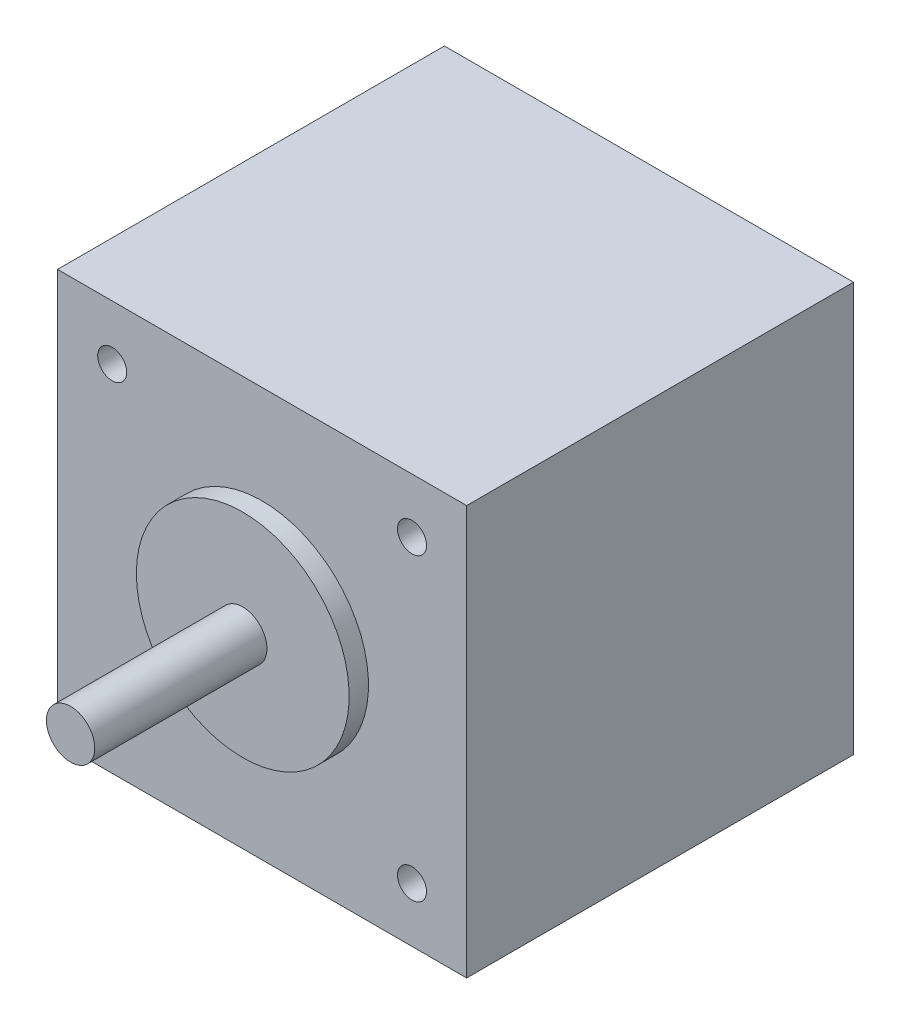
SolidWorks part; units mm, degrees
ref_plane "Спереди" through (0, 0, 0) normal (0, 0, 1) x (1, 0, 0)
ref_plane "Сверху" through (0, 0, 0) normal (0, 1, 0) x (1, 0, 0)
ref_plane "Справа" through (0, 0, 0) normal (1, 0, 0) x (0, 0, -1)
other "Configuration Table"
sketch "Эскиз1" plane through (0, 0, 0) normal (0, 0, 1) x (1, 0, 0)
  line L1 (-21.15, -21.15) -> (21.15, -21.15)
  line L2 (-21.15, -21.15) -> (-21.15, 21.15)
  line L3 (-21.15, 21.15) -> (21.15, 21.15)
  line L4 (21.15, -21.15) -> (21.15, 21.15)
  line L5 (-21.15, -21.15) -> (21.15, 21.15) construction
  line L6 (-21.15, 21.15) -> (21.15, -21.15) construction
  point P0 (0, 0)
  dimension "D1" = 42.3
  dimension "D2" = 42.3
extrude "Корпус" add sketch "Эскиз1" along normal blind 40
sketch "Эскиз2" plane through (0, 0, 0) normal (0, 0, 1) x (1, 0, 0)
  circle A0 centre (0, 0) radius 2.5
extrude "Вал_ПРЕДВ" add sketch "Эскиз2" along normal blind 59.8
sketch "Эскиз3" plane through (0, 0, 0) normal (0, 0, 1) x (1, 0, 0)
  circle A0 centre (0, 0) radius 11
  dimension "D1" = 22
extrude "Буртик_ПРЕДВ" add sketch "Эскиз3" along normal blind 42
sketch "Эскиз4" plane through (0, 0, 0) normal (0, 0, 1) x (1, 0, 0)
  circle A0 centre (0, 0) radius 8
  dimension "D1" = 16
sketch "Эскиз5" plane through (0, 0, 0) normal (0, 0, 1) x (1, 0, 0)
  circle A0 centre (-15.5, -15.5) radius 1.5
  circle A1 centre (-15.5, 15.5) radius 1.5
  circle A2 centre (15.5, -15.5) radius 1.5
  circle A3 centre (15.5, 15.5) radius 1.5
  dimension "D1" = 3
  dimension "D2" = 3
  dimension "D3" = 3
  dimension "D4" = 3
extrude "Крепеж_М3_ПРЕДВ" cut sketch "Эскиз5" against normal blind 4.5 from offset 40
equation "\"Мотор X ширина корпуса\"= 42.3"
equation "\"Мотор X высота корпуса\"= 42.3"
equation "\"Мотор X длина корпуса\"= 40"
equation "\"Мотор X вылет вала\"= 19.8"
equation "\"Мотор Y ширина корпуса\"= 42.3"
equation "\"Мотор Y высота корпуса\"= 42.3"
equation "\"Мотор Y длина корпуса\"= 48"
equation "\"Мотор Y вылет вала\"= 30"
equation "\"Мотор Z ширина корпуса\"= 42"
equation "\"Мотор Z высота корпуса\"= 42"
equation "\"Мотор Z длина корпуса\"= 40"
equation "\"Мотор Z вылет вала\"= 23"
equation "\"Мотор диаметр вала ПРЕДВ\"= 5"
equation "\"Мотор шаг крепления ПРЕДВ\"= 31"
equation "\"Мотор диаметр отверстий ПРЕДВ\"= 3"
equation "\"Мотор глубина отверстий ПРЕДВ\"= 4.5"
equation "\"Мотор диаметр буртика ПРЕДВ\"= 22"
equation "\"Мотор высота буртика ПРЕДВ\"= 2"
equation "\"Мотор диаметр шкива ПРЕДВ\"= 16"
equation "\"Мотор длина шкива ПРЕДВ\"= 12"
equation "\"Мотор отступ шкива ПРЕДВ\"= 5"
equation "\"Мотор X шаг градусов\"= 1.8"
equation "\"Мотор Y шаг градусов\"= 1.8"
equation "\"Мотор Z шаг градусов\"= 1.8"
equation "\"Мотор Y диаметр ротора\"= 25.78"
equation "\"D1@Эскиз1\" = \"Мотор X ширина корпуса\""
equation "\"D1@Корпус\" = \"Мотор X длина корпуса\""
equation "\"D1@Эскиз2\" = \"Мотор диаметр вала ПРЕДВ\""
equation "\"D1@Вал_ПРЕДВ\" = \"Мотор X длина корпуса\" + \"Мотор X вылет вала\""
equation "\"D1@Эскиз3\" = \"Мотор диаметр буртика ПРЕДВ\""
equation "\"D1@Буртик_ПРЕДВ\" = \"Мотор X длина корпуса\" + \"Мотор высота буртика ПРЕДВ\""
equation "\"D1@Эскиз4\" = \"Мотор диаметр шкива ПРЕДВ\""
equation "\"D1@Эскиз5\" = \"Мотор диаметр отверстий ПРЕДВ\""
equation "\"D2@Эскиз5\" = \"Мотор диаметр отверстий ПРЕДВ\""
equation "\"D3@Эскиз5\" = \"Мотор диаметр отверстий ПРЕДВ\""
equation "\"D4@Эскиз5\" = \"Мотор диаметр отверстий ПРЕДВ\""
equation "\"D1@Крепеж_М3_ПРЕДВ\" = \"Мотор глубина отверстий ПРЕДВ\""
equation "\"D19@Крепеж_М3_ПРЕДВ\" = \"Мотор X длина корпуса\""
equation "\"Ширина груза\"= 420"
equation "\"Глубина груза\"= 490"
equation "\"Высота груза\"= 297"
equation "\"Ширина ячейки\"= \"Ширина груза\" + 10"
equation "\"Глубина ячейки\"= \"Глубина груза\" + 10"
equation "\"Высота ячейки\"= \"Высота груза\" + 10 + 13"
equation "\"Колво ячеек ширина\"= 2"
equation "\"Колво ячеек высота\"= 2"
equation "\"Толщина стенки\"= 10"
equation "\"Крепление дверцы\"= 5"
equation "\"Ширина рейки\"= \"Толщина шестерни\""
equation "\"Высота рейки\"= 20"
equation "\"Высота пола\"= 20"
equation "\"Колво полозьев\"= 5"
equation "\"Отступ рейки\"= 20"
equation "\"Глубина каретки\"= \"Глубина ячейки\" + 30 + \"Мотор Y высота корпуса\" + 20"
equation "\"Отступ шпильки\"= 20"
equation "\"Диаметр шпильки\"= 5"
equation "\"Длинна шпильки\"= ( \"Высота ячейки\" + \"Толщина стенки\" + \"Высота пола\" ) * \"Колво ячеек высота\" + ( \"Толщина стенки\" + \"Отступ рейки\" ) * 2 "
equation "\"Ширина пластины\"= 50  "
equation "\"Высота зона выгрузки\"= \"Высота ячейки\" * 2 + \"Толщина стенки\" * 2"
equation "\"Колво выгрузки\"= 1"
equation "\"Отступ крепления мотора фиксации\" = 30"
equation "\"Диаметр оси\"= 10"
equation "\"Диаметр ролика\"= 20"
equation "\"Колво роликов\"= 10"
equation "\"Шаг роликов\"= \"Диаметр ролика\" + 20"
equation "\"Ширина ячейки выгрузки\"= \"Ширина ячейки\" + \"Толщина стенки\" + \"Отступ крепления мотора фиксации\"*2"
equation "\"Длинна рейки\"= ( \"Ширина ячейки\" + \"Толщина стенки\" + \"Крепление дверцы\" ) * \"Колво ячеек ширина\" + \"Ширина ячейки выгрузки\" * \"Колво выгрузки\" + \"Толщина стенки\""
equation "\"Толщина шестерни\"= 10"
